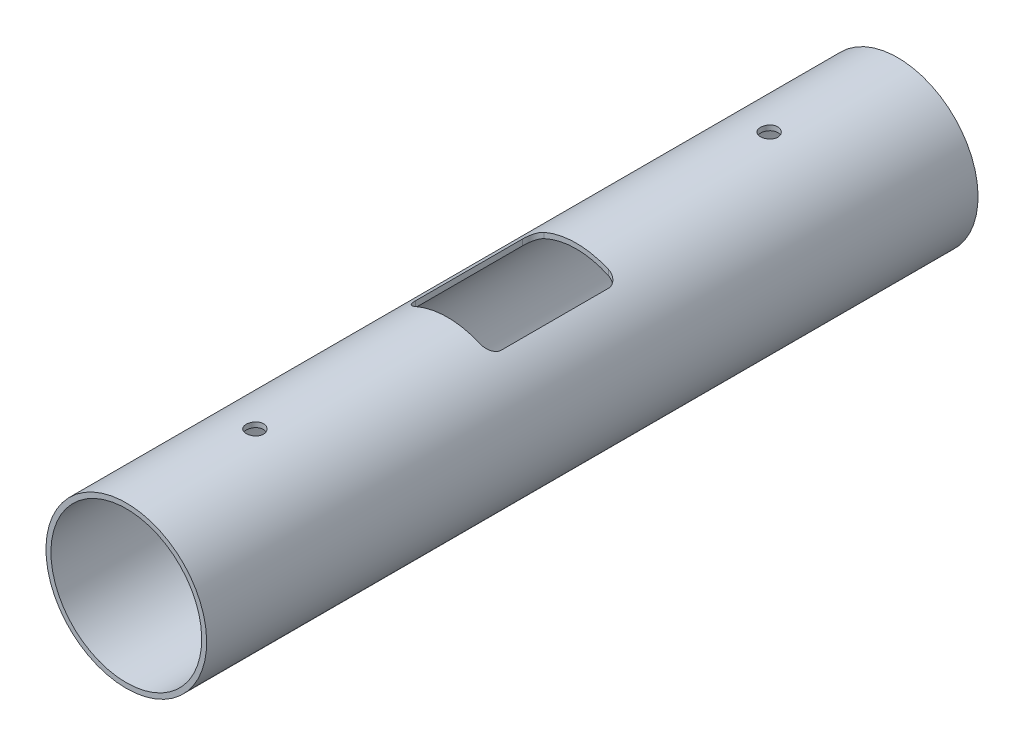
SolidWorks part; units mm, degrees
material "6061-T6 (SS)"
ref_plane "Front Plane" through (0, 0, 0) normal (0, 0, 1) x (1, 0, 0)
ref_plane "Top Plane" through (0, 0, 0) normal (0, 1, 0) x (1, 0, 0)
ref_plane "Right Plane" through (0, 0, 0) normal (1, 0, 0) x (0, 0, -1)
sketch "Sketch1" plane through (0, 0, 0) normal (0, 0, 1) x (1, 0, 0)
  line L0 (23.8125, 0) -> (22.3393, 0) construction
  circle A0 centre (0, 0) radius 23.8125
  circle A1 centre (0, 0) radius 22.3393
  point P4 (22.3393, 0)
  point P5 (23.8125, 0)
  point P6 (0, 23.8125)
  point P7 (0, 22.3393)
  dimension "OD" = 47.625
  dimension "ID" = 44.6786
  dimension "Wall Thickness" = 1.4732
sketch "Sketch2" plane through (0, 0, 0) normal (1, 0, 0) x (0, 0, -1)
  line L0 (-114.3, 0) -> (114.3, 0) construction
  line L2 (-114.3, 23.8125) -> (114.3, 23.8125) construction
  line L3 (-114.3, 23.8125) -> (-114.3, 22.3393) construction
  line L4 (-114.3, 22.3393) -> (114.3, 22.3393) construction
  line L5 (114.3, 23.8125) -> (114.3, 22.3393) construction
  line L7 (-6.35, 0) -> (6.35, 0) construction
  point P4 (0, 0)
  point P19 (0, 0)
  dimension "Length" = 228.6
sketch "Sketch3" plane through (0, 0, 0) normal (1, 0, 0) x (0, 0, -1)
  line L0 (-114.3, 0) -> (114.3, 0) construction
  line L1 (-114.3, 23.8125) -> (114.3, 23.8125)
  line L2 (-114.3, 23.8125) -> (-114.3, 22.3393)
  line L3 (-114.3, 22.3393) -> (114.3, 22.3393)
  line L4 (114.3, 23.8125) -> (114.3, 22.3393)
  line L5 (-114.3, 0) -> (114.3, 0) construction
revolve "Revolve1" add sketch "Sketch3" angle 360 about L5
sketch "Sketch4" plane through (0, 0, 0) normal (0, 1, 0) x (1, 0, 0)
  line L0 (0, 76.2) -> (0, -76.2) construction
  circle A0 centre (0, 76.2) radius 2.5527
  circle A1 centre (0, -76.2) radius 2.5527
  dimension "D1" = 5.1054
  dimension "D2" = 152.4
extrude "Cut-Extrude1" cut sketch "Sketch4" against normal through all both and the other way through all
sketch "Sketch5" plane through (0, 0, 0) normal (0, 1, 0) x (1, 0, 0)
  line L1 (9.525, -19.05) -> (-9.525, -19.05)
  line L2 (12.7, -15.875) -> (12.7, 15.875)
  line L3 (9.525, 19.05) -> (-9.525, 19.05)
  line L4 (-12.7, -15.875) -> (-12.7, 15.875)
  line L5 (12.7, -19.05) -> (-12.7, 19.05) construction
  line L6 (12.7, 19.05) -> (-12.7, -19.05) construction
  arc A0 (-9.525, -19.05) -> (-12.7, -15.875) centre (-9.525, -15.875) cw
  arc A1 (9.525, -19.05) -> (12.7, -15.875) centre (9.525, -15.875) ccw
  arc A2 (12.7, 15.875) -> (9.525, 19.05) centre (9.525, 15.875) ccw
  arc A3 (-9.525, 19.05) -> (-12.7, 15.875) centre (-9.525, 15.875) ccw
  point P0 (0, 0)
  dimension "D1" = 3.175
  dimension "D2" = 25.4
  dimension "D3" = 38.1
extrude "Cut-Extrude2" cut sketch "Sketch5" along normal through all
equation "\"ID@Sketch1\"=\"OD@Sketch1\"-(2*\"Wall Thickness@Sketch1\")"
